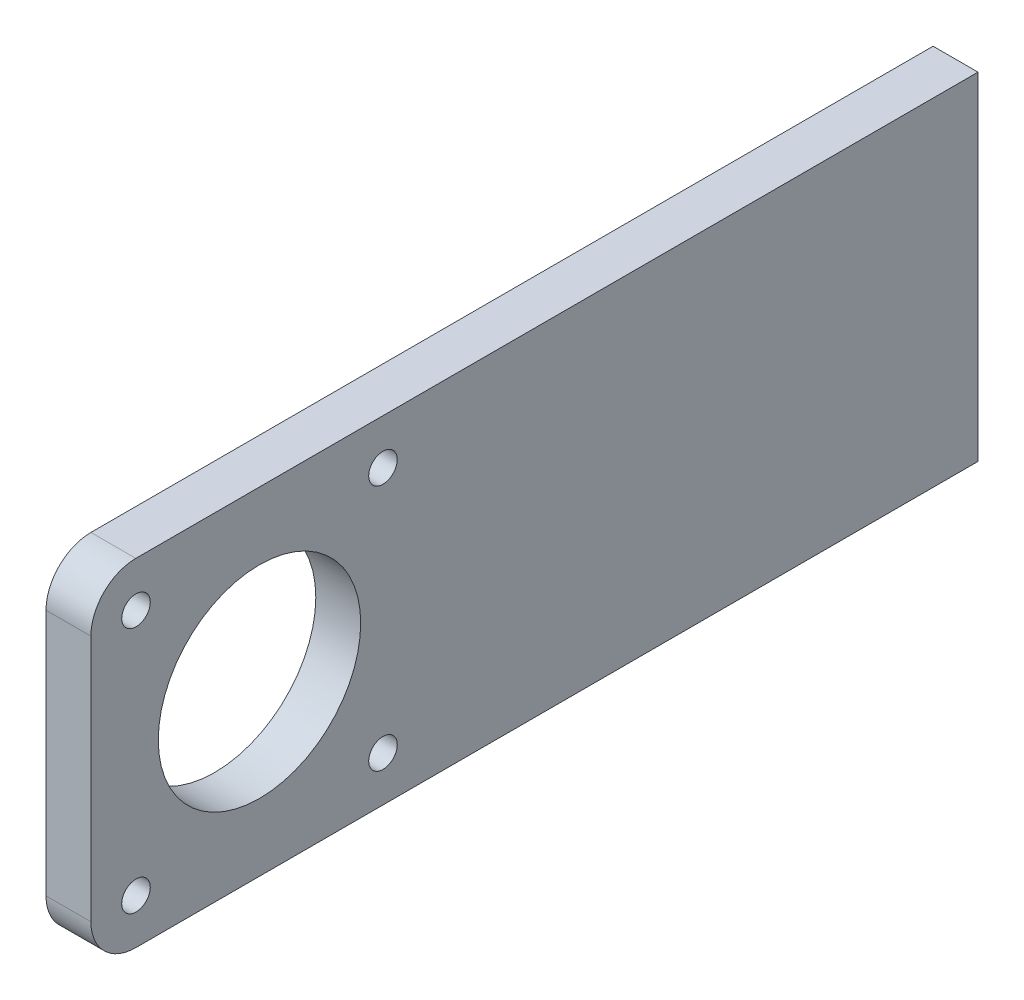
SolidWorks part; units mm, degrees
material "6061-T6 (SS)"
ref_plane "Front" through (0, 0, 0) normal (0, 0, 1) x (1, 0, 0)
ref_plane "Top" through (0, 0, 0) normal (0, 1, 0) x (1, 0, 0)
ref_plane "Right" through (0, 0, 0) normal (1, 0, 0) x (0, 0, -1)
sketch "Sketch1" plane through (0, 0, 0) normal (1, 0, 0) x (0, 0, -1)
  line L0 (0, -23.8379) -> (0, 23.8379)
  line L3 (0, 23.8379) -> (-125.4379, 23.8379)
  line L4 (-125.4379, -23.8379) -> (0, -23.8379)
  line L5 (-125.4379, 23.8379) -> (-125.4379, -23.8379)
  circle A1 centre (-101.6, 0) radius 14.3129
  point P4 (0, 0)
  point P6 (0, 0)
  dimension "D3" = 28.6258
  dimension "D1" = 9.525
  dimension "D5" = 101.6
extrude "Boss-Extrude1" add sketch "Sketch1" along normal blind 6.35
fillet "Fillet1" radius 6.35 2 edges at (3.175, -23.8379, 125.4379) (3.175, 23.8379, 125.4379)
sketch "Sketch4" plane through (0, 0, 0) normal (-1, 0, 0) x (0, 0, 1)
  point P0 (84.1375, 17.4625)
  point P3 (119.0625, 17.4625)
  point P6 (119.0625, -17.4625)
  point P9 (84.1375, -17.4625)
hole_wizard "#10-32 Tapped Hole1" positions "Sketch4" profile "Sketch3" tap size "#10-32" standard "ANSI Inch" end condition up to next
sketch "Sketch3" plane through (0, 17.4625, 84.1375) normal (0, 1, 0) x (0, 0, 1)
  line L0 (0, 0) -> (0, 6.35)
  line L1 (0, 6.35) -> (2.0193, 6.35)
  line L2 (2.0193, 6.35) -> (2.0193, 0)
  line L5 (2.0193, 0) -> (0, 0)
  line L11 (0, -6.35) -> (0, 107.95) construction
  dimension "Thru Tap Drill Dia." = 4.0386
  dimension "Thru Tap Drill Depth" = 6.35
cosmetic thread "Hole Thread1" parameters "D2"=4.826
cosmetic thread "Hole Thread2" parameters "D2"=4.826
cosmetic thread "Hole Thread3" parameters "D2"=4.826
cosmetic thread "Hole Thread4" parameters "D2"=4.826
